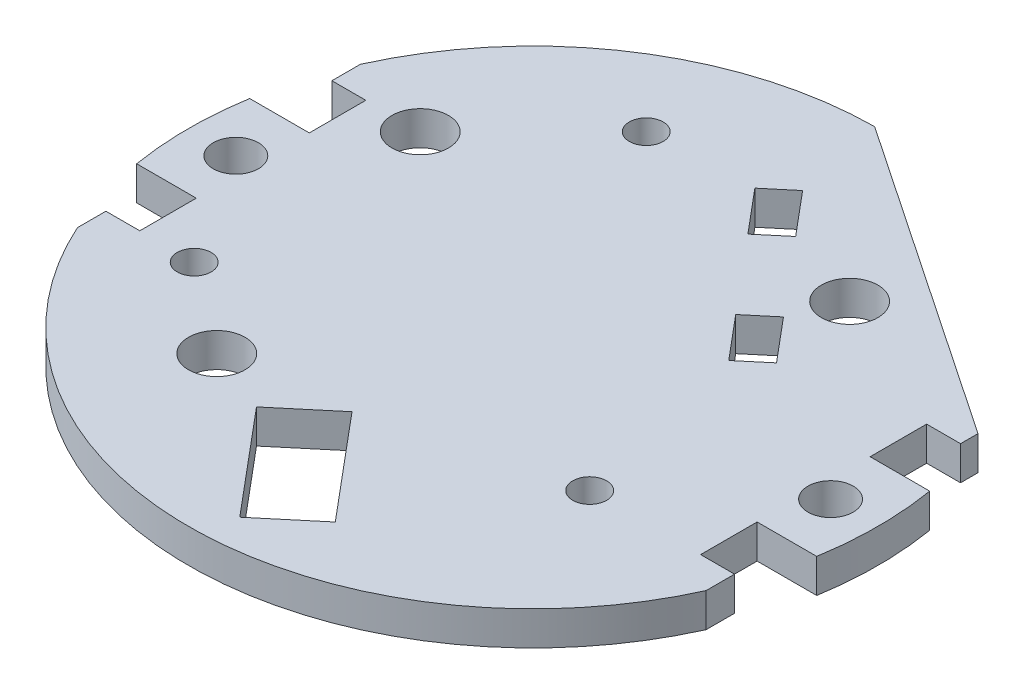
SolidWorks part; units mm, degrees
ref_plane "Alzado" through (0, 0, 0) normal (0, 0, 1) x (1, 0, 0)
ref_plane "Planta" through (0, 0, 0) normal (0, 1, 0) x (1, 0, 0)
ref_plane "Vista lateral" through (0, 0, 0) normal (1, 0, 0) x (0, 0, -1)
sketch "Croquis1" plane through (0, 0, 0) normal (0, 1, 0) x (1, 0, 0)
  circle A0 centre (0, 0) radius 30.5
extrude "Saliente-Extruir1" add sketch "Croquis1" along normal blind 3
sketch "Croquis5" plane through (0, 3, 0) normal (0, 1, 0) x (1, 0, 0)
  line L0 (0, 0) -> (0, 10)
  line L1 (28.8141, -5) -> (30.0874, -5)
  line L2 (28.8141, 5) -> (30.0874, 5)
  line L3 (-24.8141, 10) -> (-28.8141, 10)
  line L4 (24.8141, -5) -> (24.8141, -10)
  line L5 (-24.8141, -10) -> (-28.8141, -10)
  line L6 (24.8141, -5) -> (28.8141, -5)
  line L7 (24.8141, 5) -> (24.8141, 10)
  line L8 (-24.8141, 5) -> (-28.8141, 5)
  line L9 (-24.8141, 5) -> (-24.8141, 10)
  line L10 (-24.8141, -5) -> (-28.8141, -5)
  line L11 (-24.8141, -5) -> (-24.8141, -10)
  line L12 (24.8141, 5) -> (28.8141, 5)
  line L13 (24.8141, -10) -> (28.8141, -10)
  line L14 (24.8141, 10) -> (28.8141, 10)
  line L15 (-28.8141, 5) -> (-30.0874, 5)
  line L16 (-28.8141, -5) -> (-30.0874, -5)
  circle A1 centre (0, 0) radius 30.5 construction
  arc A2 (-28.8141, 10) -> (-30.0874, 5) centre (0, 0) ccw
  arc A3 (28.8141, 10) -> (28.8141, -10) centre (0, 0) cw
  arc A4 (-30.0874, -5) -> (-28.8141, -10) centre (0, 0) ccw
  arc A5 (30.0874, -5) -> (28.8141, -10) centre (0, 0) cw
  arc A6 (28.8141, 10) -> (30.0874, 5) centre (0, 0) cw
  circle M2 centre (0, 0) radius 30.5
extrude "Cortar-Extruir3" cut sketch "Croquis5" against normal blind 4 contours L11 L10 L8 L9 L3 L5 M2 | L15 L8 L9 L3 M2 | L14 L7 L12 L2 M2 | L4 L13 L1 L6 M2 region at (27.1844, 3, 7.3876) region at (27.1844, 3, -7.3876) region at (-27.1844, 3, 7.3876) region at (-27.1844, 3, -7.3876)
sketch "Croquis7" plane through (0, 3, 0) normal (0, 1, 0) x (1, 0, 0)
  line L0 (-8.1011, 29.1011) -> (9.5756, 8.0348)
  line L1 (9.5756, 8.0348) -> (27.2522, -13.0314)
  line L2 (-8.1011, 29.1011) -> (-27.2522, 13.0314)
  line L3 (27.2522, -13.0314) -> (8.1011, -29.1011)
  line L4 (8.1011, -29.1011) -> (-27.2522, 13.0314)
  line L5 (1.4284, 22.4114) -> (-0.8697, 20.4831)
  line L6 (1.4284, 22.4114) -> (4.6423, 18.5812)
  line L7 (4.6423, 18.5812) -> (2.3442, 16.6528)
  line L8 (2.3442, 16.6528) -> (-0.8697, 20.4831)
  line L9 (7.9686, 9.95) -> (11.1825, 6.1197)
  line L10 (8.1011, -29.1011) -> (5.53, -26.0369)
  line L11 (10.2667, 11.8783) -> (13.4807, 8.0481)
  line L12 (13.4807, 8.0481) -> (11.1825, 6.1197)
  line L13 (10.2667, 11.8783) -> (7.9686, 9.95)
  line L14 (5.53, -26.0369) -> (10.8923, -21.5374)
  line L15 (10.8923, -21.5374) -> (-19.3188, 14.4667)
  line L17 (-24.6811, 9.9672) -> (-19.3188, 14.4667)
  point P7 (-9.5756, -8.0348)
extrude "Cortar-Extruir5" cut sketch "Croquis7" against normal blind 4 contours L7 L6 L5 L0 | L11 L13 L0 L1 L12 region at (1.8863, 3, -19.5321) region at (10.7246, 3, -8.999)
sketch "Croquis8" plane through (0, 3, 0) normal (0, 1, 0) x (1, 0, 0)
  line L0 (-11.3137, 11.3137) -> (0, 0)
  line L2 (0, 0) -> (12, 0)
  line L3 (0, 0) -> (-11.3137, 11.3137)
  line L4 (12, 0) -> (12, 16)
  line L5 (0, 0) -> (-12, 0)
  line L6 (-12, 0) -> (-12, -16)
  line L10 (1.5586, -27.5246) -> (6.1549, -23.6679)
  line L11 (6.1549, -23.6679) -> (-1.5586, -14.4754)
  line L13 (-6.1549, -18.3321) -> (-1.5586, -14.4754)
  line L14 (1.5586, -27.5246) -> (-6.1549, -18.3321)
  circle A0 centre (0, 0) radius 30
  circle A1 centre (0, 0) radius 16
  circle A2 centre (0, 0) radius 24
  circle A3 centre (-12, -16) radius 2.5
  circle A4 centre (0, 0) radius 20
  circle A5 centre (12, 16) radius 2.5
  point P20 (-3.8567, -16.4037)
extrude "Cortar-Extruir6" cut sketch "Croquis8" against normal blind 10 contours L13 A4 L10 L11 | A4 A3 | L6 A4 A3 | A3 A4 L6 | A4 A5 | L4 A5 A4 | A4 A5 L4 | A2 L14 L10 L11 | A4 L14 A2 L11 | L13 A1 L11 region at (10.8019, 3, -15.3654) region at (12.6835, 3, -14.5491) region at (-10.8019, 3, 15.3654) region at (-12.6835, 3, 14.5491) region at (-1.7552, 3, 18.1481) region at (-1.6254, 3, 15.4208) region at (12.6194, 3, -16.8259) region at (-12.6194, 3, 16.8259) region at (0.4942, 3, 21.8146) region at (2.2344, 3, 25.0251)
sketch "Croquis9" plane through (0, 3, 0) normal (0, 1, 0) x (1, 0, 0)
  line L0 (0, 0) -> (0, 20)
  line L1 (0, 20) -> (-10, 20)
  line L2 (0, 0) -> (-20, 0)
  line L3 (-20, 0) -> (-20, -10)
  line L4 (0, 0) -> (15, 0)
  line L5 (15, 0) -> (15, -10)
  circle A0 centre (-10, 20) radius 1.5
  circle A1 centre (-20, -10) radius 1.5
  circle A2 centre (15, -10) radius 1.5
extrude "Cortar-Extruir7" cut sketch "Croquis9" against normal blind 3 contours A1 | A2 | A0 region at (-18.9693, 3, 8.9693) region at (16.0307, 3, 8.9693)
sketch "Croquis10" plane through (0, 3, 0) normal (0, 1, 0) x (1, 0, 0)
  line L0 (-24.8141, 10) -> (-27.8141, 10)
  line L2 (-24.8141, 10) -> (-28.8141, 10) construction
  line L4 (-27.8141, 10) -> (-27.8141, 12.5151)
  line L6 (-27.8141, 10) -> (-28.8141, 10)
  line L14 (-27.8141, -10) -> (-28.8141, -10)
  line L15 (-27.8141, -10) -> (-27.8141, -12.5151)
  line L16 (27.8141, -10) -> (27.8141, -12.5151)
  line L17 (27.8141, -10) -> (28.8141, -10)
  line L21 (27.8141, 10) -> (28.8141, 10)
  line L22 (27.8141, 10) -> (27.8141, 12.5151)
  line L23 (24.8141, 10) -> (27.8141, 10)
  circle A0 centre (-26.3141, 0) radius 2
  circle A1 centre (26.3141, 0) radius 2
  arc A2 (28.8141, 10) -> (-28.8141, 10) centre (0, 0) ccw construction
  arc A5 (-27.8141, 12.5151) -> (-28.8141, 10) centre (0, 0) ccw
  arc A7 (-27.8141, -12.5151) -> (-28.8141, -10) centre (0, 0) cw
  arc A8 (27.8141, -12.5151) -> (28.8141, -10) centre (0, 0) ccw
  arc A10 (27.8141, 12.5151) -> (28.8141, 10) centre (0, 0) cw
  line M13 (24.8141, 10) -> (28.8141, 10)
  arc M14 (28.8141, 10) -> (-28.8141, 10) centre (0, 0) ccw
  line M15 (-28.8141, 10) -> (-24.8141, 10)
  line M21 (-24.8141, -10) -> (-28.8141, -10)
  arc M22 (-28.8141, -10) -> (28.8141, -10) centre (0, 0) ccw
  line M23 (28.8141, -10) -> (24.8141, -10)
extrude "Cortar-Extruir8" cut sketch "Croquis10" against normal blind 3 contours L15 M21 M22 | L4 M15 M14 | L16 M23 M22 | L22 M13 M14 | A0 | A1 | L22 A10 L21 region at (-28.1547, 3, -10.8559) region at (28.1547, 3, -10.8559) region at (-28.1547, 3, 10.8559) region at (28.1547, 3, 10.8559) region at (-26.3141, 3, 0) region at (26.3141, 3, 0)
sketch "Croquis11" plane through (0, 3, 0) normal (0, 1, 0) x (1, 0, 0)
  line L0 (0, 0) -> (-20, 0)
  line L1 (-20, 0) -> (-20, 10)
  line L2 (0, 0) -> (0, 4.5949)
  line L3 (29.8013, 10.2046) -> (-1.7022, 31.454)
  circle A0 centre (-20, 10) radius 2.5
  circle A5 centre (0, 0) radius 31.5
  line M20 (27.8141, 10) -> (27.8141, 12.5151)
  arc M21 (27.8141, 12.5151) -> (-27.8141, 12.5151) centre (0, 0) ccw
extrude "Cortar-Extruir9" cut sketch "Croquis11" against normal blind 3 contours L3 M20 M21 | A0 region at (15.2326, 3, -22.6507) region at (-18.2822, 3, -8.2822)
